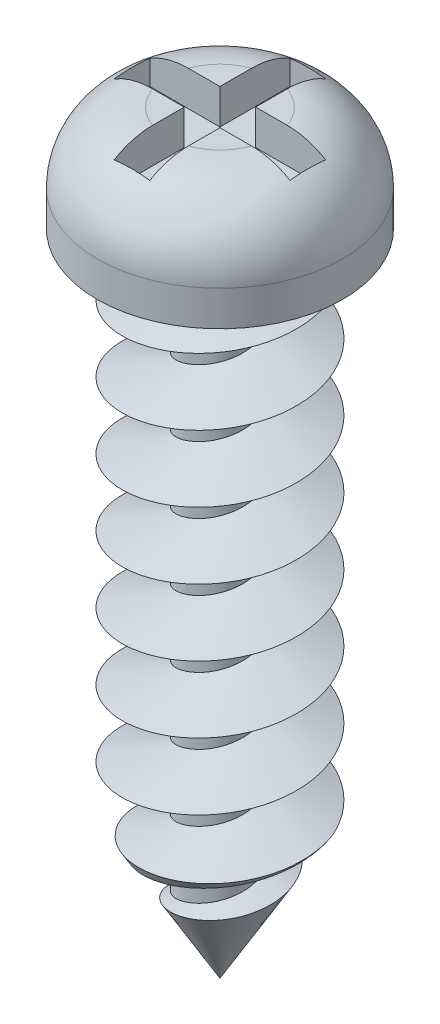
SolidWorks part; units mm, degrees
material "Aço carbono simples"
ref_plane "Plano frontal" through (0, 0, 0) normal (0, 0, 1) x (1, 0, 0)
ref_plane "Plano superior" through (0, 0, 0) normal (0, 1, 0) x (1, 0, 0)
ref_plane "Plano direito" through (0, 0, 0) normal (1, 0, 0) x (0, 0, -1)
sketch "Esboço1" plane through (0, 0, 0) normal (0, 1, 0) x (1, 0, 0)
  circle A0 centre (0, 0) radius 3.5
  dimension "D1" = 7
extrude "Ressalto-extrusão1" add sketch "Esboço1" along normal blind 2
sketch "Esboço2" plane through (0, 0, 0) normal (0, -1, 0) x (1, 0, 0)
  circle A0 centre (0, 0) radius 1
extrude "Ressalto-extrusão2" add sketch "Esboço2" along normal blind 18.5
sketch "Esboço4" plane through (0, 2, 0) normal (0, 1, 0) x (1, 0, 0)
  circle A0 centre (0, 0) radius 3.5
extrude "Ressalto-extrusão3" add sketch "Esboço4" along normal blind 1
fillet "Filete1" radius 2 1 edges at (0, 3, 3.5)
sketch "Esboço5" plane through (0, 3, 0) normal (0, 1, 0) x (1, 0, 0)
  line L0 (-0.5091, 2.5066) -> (0.5091, 2.5066)
  line L1 (0.5091, 2.5066) -> (0.5091, 0.5091)
  line L2 (-0.5091, 2.5066) -> (-0.5091, 0.5091)
  line L3 (2.5066, -0.5091) -> (0.5091, -0.5091)
  line L4 (2.5066, 0.5091) -> (0.5091, 0.5091)
  line L5 (2.5066, 0.5091) -> (2.5066, -0.5091)
  line L6 (-0.5091, -2.5066) -> (-0.5091, -0.5091)
  line L7 (0.5091, -2.5066) -> (0.5091, -0.5091)
  line L8 (0.5091, -2.5066) -> (-0.5091, -2.5066)
  line L9 (-2.5066, 0.5091) -> (-0.5091, 0.5091)
  line L10 (-2.5066, -0.5091) -> (-0.5091, -0.5091)
  line L11 (-2.5066, -0.5091) -> (-2.5066, 0.5091)
  point P2 (0, 2.5066)
  point P21 (0, 0)
  dimension "D1" = 4
extrude "Corte-extrusão1" cut sketch "Esboço5" against normal blind 1
sketch "Esboço7" plane through (0, -18.5, 0) normal (0, -1, 0) x (1, 0, 0)
  circle A0 centre (0, 0) radius 1 construction
  circle A1 centre (0, 0) radius 1
curve "Hélice/Espiral1" pitch 1.9 height 19.95 radius 1 centre (0, -18.5, 0) axis (0, 1, 0) start towards (0, 0, -1)
sketch "Esboço8" plane through (0, 0, 0) normal (0, 0, 1) x (1, 0, 0)
  line L0 (-1, -18.5) -> (-1, -19.7)
  line L1 (-1, -19.7) -> (-2.5, -19.1)
  line L2 (-2.5, -19.1) -> (-1, -18.5)
  point P4 (-1, -19.1)
  dimension "D1" = 1.5
  dimension "D2" = 1.2
sweep "Varredura1" add profiles "Esboço8" path "Hélice/Espiral1"
sketch "Esboço10" plane through (0, 0, 0) normal (0, 0, 1) x (1, 0, 0)
  line L0 (0, -18.5109) -> (-4.5745, -10.6899)
  line L1 (-4.5745, -10.6899) -> (-7.3132, -12.2918)
  line L2 (-7.3132, -12.2918) -> (-2.2156, -21.9789)
  line L3 (-2.2156, -21.9789) -> (0, -20.4992)
  line L4 (0, -20.4992) -> (0, -18.5109)
revolve "Corte-Revolução1" cut sketch "Esboço10" angle 360 about L4
